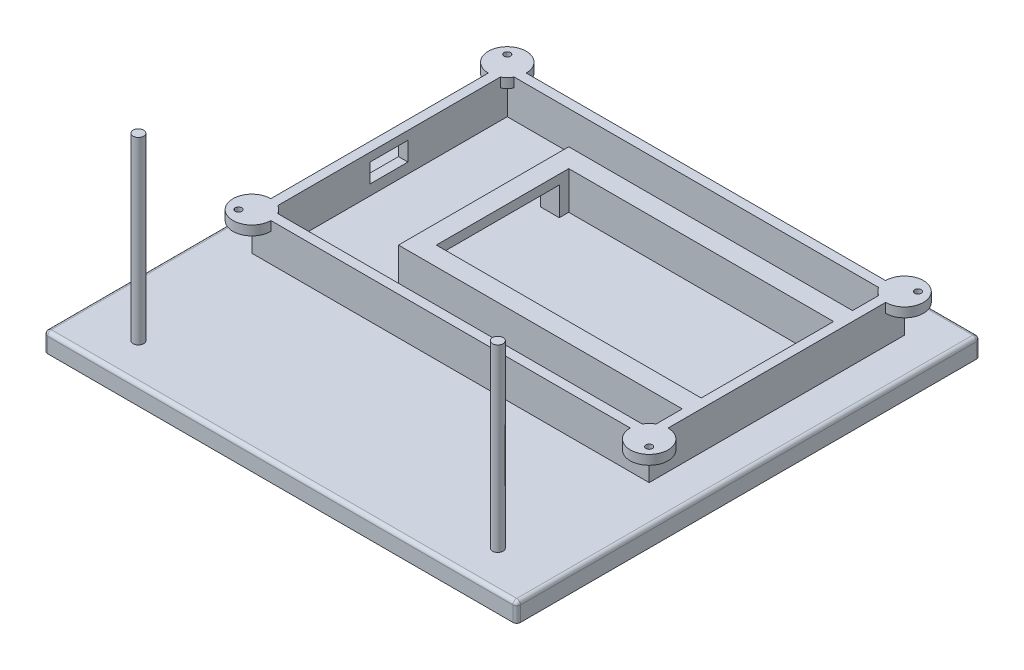
SolidWorks part; units mm, degrees
ref_plane "Front Plane" through (0, 0, 0) normal (0, 0, 1) x (1, 0, 0)
ref_plane "Top Plane" through (0, 0, 0) normal (0, 1, 0) x (1, 0, 0)
ref_plane "Right Plane" through (0, 0, 0) normal (1, 0, 0) x (0, 0, -1)
sketch "Sketch1" plane through (0, 0, 0) normal (0, 1, 0) x (1, 0, 0)
  line L0 (0, 0) -> (210, 0)
  line L1 (210, 0) -> (210, -135)
  line L2 (210, -135) -> (0, -135)
  line L3 (0, -135) -> (0, 0)
  line L4 (0, 0) -> (5, 0)
  line L5 (5, 0) -> (5, -130)
  line L6 (5, -130) -> (205, -130)
  line L7 (205, -130) -> (205, -5)
  line L8 (205, -5) -> (5, -5)
extrude "Boss-Extrude3" add sketch "Sketch1" along normal blind 40 contours L8 L7 L6 L5 L0 L3 L2 L1 region at (2.5, 0, 2.4965)
sketch "Sketch3" plane through (0, 0, 0) normal (0, -1, 0) x (-1, 0, 0)
  line L0 (0, -135) -> (0, -145)
  line L1 (0, -145) -> (-220, -145)
  line L2 (-220, -145) -> (-220, 10)
  line L3 (-220, 10) -> (10, 10)
  line L4 (10, 10) -> (10, -145)
  line L5 (10, -145) -> (0, -145)
  line M6 (-5, -5) -> (-5, -130)
  line M7 (-5, -130) -> (-205, -130)
  line M8 (-205, -130) -> (-205, -5)
  line M9 (-205, -5) -> (-5, -5)
  line M10 (-210, 0) -> (-210, -135)
  line M11 (-210, -135) -> (0, -135)
  line M12 (0, -135) -> (0, 0)
  line M13 (0, 0) -> (-210, 0)
extrude "Boss-Extrude4" add sketch "Sketch3" along normal blind 10 contours M6 M9 M8 M7 | L5 L4 L3 L2 L1 M11 M10 M13 M12 | M13 M10 M11 M12 M9 M6 M7 M8 region at (110, 0, 142.2265) region at (105, 0, 132.5035) region at (105, 0, 67.5)
sketch "Sketch4" plane through (0, 0, 0) normal (0, 1, 0) x (1, 0, 0)
  line L0 (205, -67.5) -> (205, -32.5)
  line L1 (205, -130) -> (205, -5) construction
  line L2 (205, -32.5) -> (65, -32.5)
  line L3 (65, -32.5) -> (65, -102.5)
  line L4 (65, -102.5) -> (205, -102.5)
  line L5 (205, -102.5) -> (205, -67.5)
  line L6 (205, -32.5) -> (205, -27.5)
  line L7 (205, -130) -> (205, -5) construction
  line L8 (205, -27.5) -> (60, -27.5)
  line L9 (60, -27.5) -> (60, -107.5)
  line L10 (60, -107.5) -> (205, -107.5)
  line L11 (205, -107.5) -> (205, -102.5)
extrude "Extrude-Thin1" add sketch "Sketch4" along normal blind 40 thin contours L2 L3 L4 thin type one direction wall 10
sketch "Sketch5" plane through (55, 0, 0) normal (-1, 0, 0) x (0, 0, 1)
  line L0 (67.5, 0) -> (67.5, 15)
  line L1 (-10, 0) -> (145, 0) construction
  line L2 (67.5, 15) -> (97.5, 15)
  line L3 (97.5, 15) -> (97.5, 0)
  line L4 (135, 0) -> (0, 0) construction
  line L5 (97.5, 0) -> (37.5, 0)
  line L6 (37.5, 0) -> (37.5, 15)
  line L7 (37.5, 15) -> (67.5, 15)
extrude "Cut-Extrude2" cut sketch "Sketch5" against normal blind 40 contours L3 L2 L0 L1 | L7 L6 L1 L0 region at (55, 7.5, 52.5) region at (55, 7.5, 82.5)
sketch "Sketch6" plane through (0, 40, 0) normal (0, 1, 0) x (1, 0, 0)
  line L0 (0, 0) -> (210, 0)
  line L1 (210, 0) -> (210, -135) construction
  line L2 (0, 0) -> (210, 0) construction
  line L3 (210, 0) -> (210, -135)
  line L4 (210, -135) -> (0, -135)
  line L5 (0, -135) -> (0, 0)
extrude "Cut-Extrude3" cut sketch "Sketch6" against normal blind 20
sketch "Sketch7" plane through (0, 20, 0) normal (0, 1, 0) x (1, 0, 0)
  circle A0 centre (0, 0) radius 10
  circle A1 centre (210, 0) radius 10
  circle A2 centre (210, -135) radius 10
  circle A3 centre (0, -135) radius 10
extrude "Boss-Extrude5" add sketch "Sketch7" against normal blind 5
sketch "Sketch8" plane through (0, 20, 0) normal (0, 1, 0) x (1, 0, 0)
  line L0 (0, 0) -> (-7.0711, 7.0711)
  line L1 (217.0711, 7.0711) -> (210, 0)
  line L2 (217.0711, -142.0711) -> (210, -135)
  line L3 (-7.0711, -142.0711) -> (0, -135)
  arc A0 (10, 0) -> (0, -10) centre (0, 0) ccw construction
  arc A1 (210, -10) -> (200, 0) centre (210, 0) ccw construction
  arc A2 (200, -135) -> (210, -125) centre (210, -135) ccw construction
  arc A3 (0, -125) -> (10, -135) centre (0, -135) ccw construction
  circle A4 centre (-3.5355, 3.5355) radius 1.7
  circle A5 centre (213.5355, 3.5355) radius 1.7
  circle A6 centre (213.5355, -138.5355) radius 1.7
  circle A7 centre (-3.5355, -138.5355) radius 1.7
extrude "Cut-Extrude5" cut sketch "Sketch8" against normal blind 5 contours A6 | A5 | A4 | A7
sketch "Sketch9" plane through (0, 0, 0) normal (-1, 0, 0) x (0, 0, 1)
  line L0 (67.5, 0) -> (67.5, 10.5)
  line L1 (135, 0) -> (0, 0) construction
  line L2 (67.5, 10.5) -> (77.5, 10.5)
  line L3 (77.5, 10.5) -> (77.5, 5.5)
  line L4 (77.5, 5.5) -> (57.5, 5.5)
  line L5 (57.5, 5.5) -> (57.5, 10.5)
  line L6 (57.5, 10.5) -> (67.5, 10.5)
  line L7 (57.5, 10.5) -> (57.5, 15.5)
  line L8 (57.5, 15.5) -> (77.5, 15.5)
  line L9 (77.5, 15.5) -> (77.5, 10.5)
  line L10 (77.5, 15.5) -> (77.5, 10.5)
extrude "Cut-Extrude6" cut sketch "Sketch9" against normal blind 10 contours L9 L8 L7 L6 L2 | L4 L3 L2 L0 | L6 L5 L4 L0 region at (0, 8, 62.5) region at (0, 8, 72.5) region at (0, 13, 67.5)
sketch "Sketch10" plane through (0, 0, 0) normal (0, 1, 0) x (1, 0, 0)
  line L0 (-10, 10) -> (-10, 20)
  line L1 (-10, 20) -> (230, 20)
  line L2 (230, 20) -> (230, -225)
  line L3 (230, -225) -> (-20, -225)
  line L4 (-20, -225) -> (-20, 20)
  line L5 (-20, 20) -> (-10, 20)
  line L6 (-10, 10) -> (220, 10)
  line L7 (220, 10) -> (220, -145)
  line L8 (220, -145) -> (-10, -145)
  line L9 (-10, -145) -> (-10, 10)
extrude "Boss-Extrude6" add sketch "Sketch10" against normal blind 10 contours L5 L4 L3 L2 L1 L6 L8 L7 region at (105, 0, 151.2402)
sketch "Sketch13" plane through (0, 0, 0) normal (-1, 0, 0) x (0, 0, 1)
  line L0 (135, 0) -> (205, 0)
  line L1 (225, 0) -> (-20, 0) construction
sketch "Sketch14" plane through (0, 0, 0) normal (0, 1, 0) x (1, 0, 0)
  line L0 (0, -205) -> (10, -205)
  line L1 (0, -135) -> (0, -205) construction
  line L2 (230, -205) -> (200, -205)
  line L3 (230, 20) -> (230, -225) construction
  circle A0 centre (10, -205) radius 2.8
  circle A1 centre (200, -205) radius 2.8
extrude "Boss-Extrude7" add sketch "Sketch14" along normal blind 95 contours A1 | A0 region at (10, 0, 207.7208) region at (197.2792, 0, 205)
fillet "Fillet1" radius 2 8 edges at (-20, -5, -20) (-20, -5, 225) (230, -5, 225) (230, -5, -20) (105, 0, -20) (230, 0, 102.5) (-20, 0, 102.5) (105, 0, 225)
